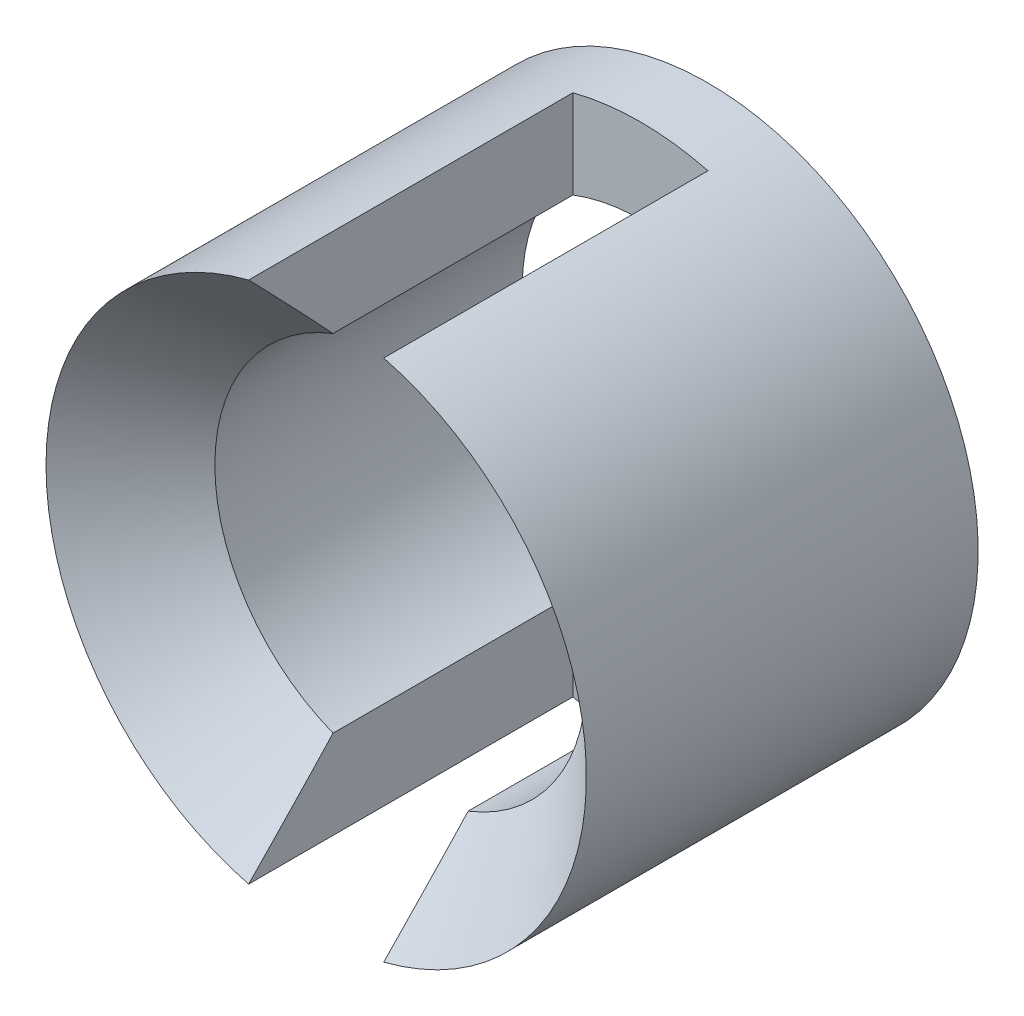
SolidWorks part; units mm, degrees
ref_plane "Ebene vorne" through (0, 0, 0) normal (0, 0, 1) x (1, 0, 0)
ref_plane "Ebene oben" through (0, 0, 0) normal (0, 1, 0) x (1, 0, 0)
ref_plane "Ebene rechts" through (0, 0, 0) normal (1, 0, 0) x (0, 0, -1)
sketch "Skizze2" plane through (0, 0, 0) normal (0, 1, 0) x (1, 0, 0)
  line L0 (48, -35) -> (52, -35) construction
  line L1 (52, -29) -> (52, -35) construction
  line L2 (52, -28) -> (52, -29) construction
  line L3 (52, -28) -> (48, -28) construction
  line L4 (48, -28) -> (48, -29) construction
  line L5 (48, -29) -> (48, -35) construction
  line L6 (48, -35) -> (52, -35)
  line L7 (52, -29) -> (52, -35)
  line L8 (52, -28) -> (52, -29)
  line L9 (52, -28) -> (48, -28)
  line L10 (48, -28) -> (48, -29)
  line L11 (48, -29) -> (48, -35)
revolve "Rotation1" add sketch "Skizze2" angle 360 about L7
hole_wizard "Formsenkung für M5 Linsensenkschraube mit Schlitz1" positions "Skizze4" profile "Skizze6" countersink size "M5" standard "DIN" end condition up to next
sketch "Skizze4" plane through (0, 0, 35) normal (0, 0, 1) x (1, 0, 0)
  point P0 (52, 0)
sketch "Skizze6" plane through (52, 0, 35) normal (1, 0, 0) x (0, -1, 0)
  line L0 (0, 0) -> (0, 7)
  line L1 (0, 7) -> (2.75, 7)
  line L2 (2.75, 7) -> (2.75, 2.45)
  line L3 (2.75, 2.45) -> (5.2, 0)
  line L5 (5.2, 0) -> (0, 0)
  line L6 (-2.75, 2.45) -> (-5.2, 0) construction
  line L11 (0, -6.35) -> (0, 107.95) construction
  dimension "Bohrerdurchmesser" = 5.5
  dimension "Bohrungstiefe" = 7
  dimension "Senkdurchmesser (Oben)" = 10.4
  dimension "Senkwinkel (Oben)" = 90
sketch "Skizze7" plane through (0, 0, 0) normal (0, 1, 0) x (1, 0, 0)
  line L0 (48, -35) -> (52, -35) construction
  line L1 (52, -29) -> (52, -35) construction
  line L2 (51, -29) -> (51, -35) construction
  line L3 (52, -29) -> (48, -29) construction
  line L4 (51, -35) -> (52, -35)
  line L5 (52, -29) -> (52, -35)
  line L6 (51, -29) -> (51, -35)
  line L7 (52, -29) -> (51, -29)
extrude "Schnitt-Linear austragen1" cut sketch "Skizze7" against normal through all both and the other way through all
mirror "Spiegeln1" about plane through (52, -4, 29) normal (1, 0, 0) of "Schnitt-Linear austragen1"
